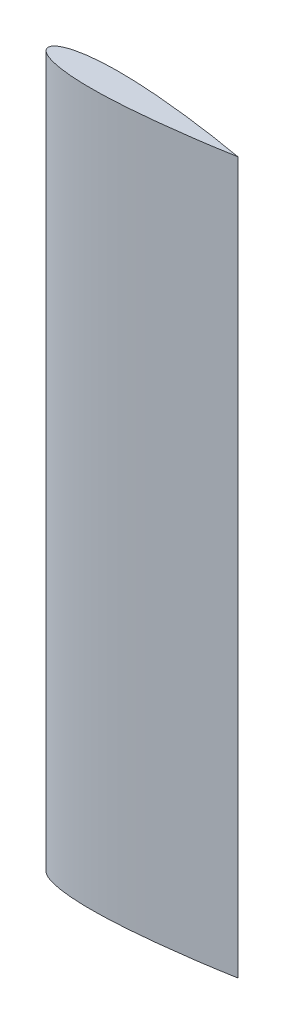
SolidWorks part; units mm, degrees
ref_plane "Front Plane" through (0, 0, 0) normal (0, 0, 1) x (1, 0, 0)
ref_plane "Top Plane" through (0, 0, 0) normal (0, 1, 0) x (1, 0, 0)
ref_plane "Right Plane" through (0, 0, 0) normal (1, 0, 0) x (0, 0, -1)
sketch "rootSketch" plane through (0, 0, 0) normal (0, 1, 0) x (1, 0, 0)
  line L0 (0, 0) -> (1500, 0) construction
  line L2 (13, -3.9) -> (13, 3.9) construction
  line L3 (0, 0) -> (52, 0) construction
  spline S0 degree 4 poles (0, 0) (0, 0.0566) (0.0054, 0.148) (0.0261, 0.2802) (0.0778, 0.4522) (0.1471, 0.6119) (0.2485, 0.786) (0.3924, 0.9775) (0.5992, 1.1954) (0.9058, 1.4518) (1.3705, 1.7579) (2.0783, 2.1191) (3.1757, 2.542) (4.8233, 2.9987) (7.2754, 3.453) (10.4387, 3.7805) (14.1293, 3.9293) (18.1436, 3.8963) (22.1517, 3.7223) (25.6562, 3.476) (28.6515, 3.2136) (31.6507, 2.914) (34.1342, 2.6396) (36.6395, 2.3366) (39.5995, 1.9537) (42.1279, 1.6007) (44.5332, 1.2475) (47.1211, 0.8374) (48.9103, 0.5455) (51.4233, 0.1075) (52.8542, -0.154) (54.9428, -0.5501) (55.9597, -0.7584) (56.7861, -0.9233) (56.9961, -0.9696) (57.2092, -1.0126) knots 0 0 0 0 0 0.003841 0.006235 0.009072 0.012193 0.015657 0.019917 0.025339 0.032593 0.042799 0.057705 0.079311 0.112503 0.158973 0.227236 0.2955 0.363764 0.432028 0.500292 0.534424 0.568556 0.63682 0.670952 0.705084 0.773347 0.807479 0.841611 0.875743 0.909875 0.954938 0.977469 0.988734 1 1 1 1 1 construction
  spline S1 degree 4 poles (0, 0) (0, 0.0566) (0.0054, 0.148) (0.0261, 0.2802) (0.0778, 0.4522) (0.1471, 0.6119) (0.2485, 0.786) (0.3924, 0.9775) (0.5992, 1.1954) (0.9058, 1.4518) (1.3705, 1.7579) (2.0783, 2.1191) (3.1757, 2.542) (4.8233, 2.9987) (7.2754, 3.453) (10.4387, 3.7805) (14.1293, 3.9293) (18.1436, 3.8963) (22.1517, 3.7223) (25.6562, 3.476) (28.6515, 3.2136) (31.6507, 2.914) (34.1342, 2.6396) (36.6395, 2.3366) (39.5995, 1.9537) (42.1279, 1.6007) (44.5332, 1.2475) (47.1211, 0.8374) (48.9103, 0.5455) (50.6553, 0.2414) (51.551, 0.0816) (52, 0) knots 0 0 0 0 0 0.003841 0.006235 0.009072 0.012193 0.015657 0.019917 0.025339 0.032593 0.042799 0.057705 0.079311 0.112503 0.158973 0.227236 0.2955 0.363764 0.432028 0.500292 0.534424 0.568556 0.63682 0.670952 0.705084 0.773347 0.807479 0.841611 0.875743 0.909875 0.909875 0.909875 0.909875 0.909875
  spline S2 degree 4 poles (0, 0) (0, -0.0566) (0.0054, -0.148) (0.0261, -0.2802) (0.0778, -0.4522) (0.1471, -0.6119) (0.2485, -0.786) (0.3924, -0.9775) (0.5992, -1.1954) (0.9058, -1.4518) (1.3705, -1.7579) (2.0783, -2.1191) (3.1757, -2.542) (4.8233, -2.9987) (7.2754, -3.453) (10.4387, -3.7805) (14.1293, -3.9293) (18.1436, -3.8963) (22.1517, -3.7223) (25.6562, -3.476) (28.6515, -3.2136) (31.6507, -2.914) (34.1342, -2.6396) (36.6395, -2.3366) (39.5995, -1.9537) (42.1279, -1.6007) (44.5332, -1.2475) (47.1211, -0.8374) (48.9103, -0.5455) (51.4233, -0.1075) (52.8542, 0.154) (54.9428, 0.5501) (55.9597, 0.7584) (56.7861, 0.9233) (56.9961, 0.9696) (57.2092, 1.0126) knots 0 0 0 0 0 0.003841 0.006235 0.009072 0.012193 0.015657 0.019917 0.025339 0.032593 0.042799 0.057705 0.079311 0.112503 0.158973 0.227236 0.2955 0.363764 0.432028 0.500292 0.534424 0.568556 0.63682 0.670952 0.705084 0.773347 0.807479 0.841611 0.875743 0.909875 0.954938 0.977469 0.988734 1 1 1 1 1 construction
  spline S3 degree 4 poles (0, 0) (0, -0.0566) (0.0054, -0.148) (0.0261, -0.2802) (0.0778, -0.4522) (0.1471, -0.6119) (0.2485, -0.786) (0.3924, -0.9775) (0.5992, -1.1954) (0.9058, -1.4518) (1.3705, -1.7579) (2.0783, -2.1191) (3.1757, -2.542) (4.8233, -2.9987) (7.2754, -3.453) (10.4387, -3.7805) (14.1293, -3.9293) (18.1436, -3.8963) (22.1517, -3.7223) (25.6562, -3.476) (28.6515, -3.2136) (31.6507, -2.914) (34.1342, -2.6396) (36.6395, -2.3366) (39.5995, -1.9537) (42.1279, -1.6007) (44.5332, -1.2475) (47.1211, -0.8374) (48.9103, -0.5455) (50.6553, -0.2414) (51.551, -0.0816) (52, 0) knots 0 0 0 0 0 0.003841 0.006235 0.009072 0.012193 0.015657 0.019917 0.025339 0.032593 0.042799 0.057705 0.079311 0.112503 0.158973 0.227236 0.2955 0.363764 0.432028 0.500292 0.534424 0.568556 0.63682 0.670952 0.705084 0.773347 0.807479 0.841611 0.875743 0.909875 0.909875 0.909875 0.909875 0.909875
  point P10 (13, 0)
  dimension "incidenceAngle" = 0
  dimension "rootChord" = 52
  dimension "rootQuarterChord" = 13
  dimension "rootMaxThickness" = 7.8
ref_plane "Plane1" through (0, 195, 0) normal (0, 1, 0) x (1, 0, 0)
sketch "tipSketch" plane through (0, 195, 0) normal (0, 1, 0) x (1, 0, 0)
  line L0 (216.8234, 0) -> (518.1352, 0) construction
  line L3 (0, 0) -> (52, 0) construction
  line L4 (13, -3.9) -> (13, 3.9) construction
  spline S0 degree 4 poles (0, 0) (0, 0.0566) (0.0054, 0.148) (0.0261, 0.2802) (0.0778, 0.4522) (0.1471, 0.6119) (0.2485, 0.786) (0.3924, 0.9775) (0.5992, 1.1954) (0.9058, 1.4518) (1.3705, 1.7579) (2.0783, 2.1191) (3.1757, 2.542) (4.8233, 2.9987) (7.2754, 3.453) (10.4387, 3.7805) (14.1293, 3.9293) (18.1436, 3.8963) (22.1517, 3.7223) (25.6562, 3.476) (28.6515, 3.2136) (31.6507, 2.914) (34.1342, 2.6396) (36.6395, 2.3366) (39.5995, 1.9537) (42.1279, 1.6007) (44.5332, 1.2475) (47.1211, 0.8374) (48.9103, 0.5455) (51.4233, 0.1075) (52.8542, -0.154) (54.9428, -0.5501) (55.9597, -0.7584) (56.7861, -0.9233) (56.9961, -0.9696) (57.2092, -1.0126) knots 0 0 0 0 0 0.003841 0.006235 0.009072 0.012193 0.015657 0.019917 0.025339 0.032593 0.042799 0.057705 0.079311 0.112503 0.158973 0.227236 0.2955 0.363764 0.432028 0.500292 0.534424 0.568556 0.63682 0.670952 0.705084 0.773347 0.807479 0.841611 0.875743 0.909875 0.954938 0.977469 0.988734 1 1 1 1 1 construction
  spline S1 degree 4 poles (0, 0) (0, 0.0566) (0.0054, 0.148) (0.0261, 0.2802) (0.0778, 0.4522) (0.1471, 0.6119) (0.2485, 0.786) (0.3924, 0.9775) (0.5992, 1.1954) (0.9058, 1.4518) (1.3705, 1.7579) (2.0783, 2.1191) (3.1757, 2.542) (4.8233, 2.9987) (7.2754, 3.453) (10.4387, 3.7805) (14.1293, 3.9293) (18.1436, 3.8963) (22.1517, 3.7223) (25.6562, 3.476) (28.6515, 3.2136) (31.6507, 2.914) (34.1342, 2.6396) (36.6395, 2.3366) (39.5995, 1.9537) (42.1279, 1.6007) (44.5332, 1.2475) (47.1211, 0.8374) (48.9103, 0.5455) (50.6553, 0.2414) (51.551, 0.0816) (52, 0) knots 0 0 0 0 0 0.003841 0.006235 0.009072 0.012193 0.015657 0.019917 0.025339 0.032593 0.042799 0.057705 0.079311 0.112503 0.158973 0.227236 0.2955 0.363764 0.432028 0.500292 0.534424 0.568556 0.63682 0.670952 0.705084 0.773347 0.807479 0.841611 0.875743 0.909875 0.909875 0.909875 0.909875 0.909875
  spline S2 degree 4 poles (0, 0) (0, -0.0566) (0.0054, -0.148) (0.0261, -0.2802) (0.0778, -0.4522) (0.1471, -0.6119) (0.2485, -0.786) (0.3924, -0.9775) (0.5992, -1.1954) (0.9058, -1.4518) (1.3705, -1.7579) (2.0783, -2.1191) (3.1757, -2.542) (4.8233, -2.9987) (7.2754, -3.453) (10.4387, -3.7805) (14.1293, -3.9293) (18.1436, -3.8963) (22.1517, -3.7223) (25.6562, -3.476) (28.6515, -3.2136) (31.6507, -2.914) (34.1342, -2.6396) (36.6395, -2.3366) (39.5995, -1.9537) (42.1279, -1.6007) (44.5332, -1.2475) (47.1211, -0.8374) (48.9103, -0.5455) (51.4233, -0.1075) (52.8542, 0.154) (54.9428, 0.5501) (55.9597, 0.7584) (56.7861, 0.9233) (56.9961, 0.9696) (57.2092, 1.0126) knots 0 0 0 0 0 0.003841 0.006235 0.009072 0.012193 0.015657 0.019917 0.025339 0.032593 0.042799 0.057705 0.079311 0.112503 0.158973 0.227236 0.2955 0.363764 0.432028 0.500292 0.534424 0.568556 0.63682 0.670952 0.705084 0.773347 0.807479 0.841611 0.875743 0.909875 0.954938 0.977469 0.988734 1 1 1 1 1 construction
  spline S3 degree 4 poles (0, 0) (0, -0.0566) (0.0054, -0.148) (0.0261, -0.2802) (0.0778, -0.4522) (0.1471, -0.6119) (0.2485, -0.786) (0.3924, -0.9775) (0.5992, -1.1954) (0.9058, -1.4518) (1.3705, -1.7579) (2.0783, -2.1191) (3.1757, -2.542) (4.8233, -2.9987) (7.2754, -3.453) (10.4387, -3.7805) (14.1293, -3.9293) (18.1436, -3.8963) (22.1517, -3.7223) (25.6562, -3.476) (28.6515, -3.2136) (31.6507, -2.914) (34.1342, -2.6396) (36.6395, -2.3366) (39.5995, -1.9537) (42.1279, -1.6007) (44.5332, -1.2475) (47.1211, -0.8374) (48.9103, -0.5455) (50.6553, -0.2414) (51.551, -0.0816) (52, 0) knots 0 0 0 0 0 0.003841 0.006235 0.009072 0.012193 0.015657 0.019917 0.025339 0.032593 0.042799 0.057705 0.079311 0.112503 0.158973 0.227236 0.2955 0.363764 0.432028 0.500292 0.534424 0.568556 0.63682 0.670952 0.705084 0.773347 0.807479 0.841611 0.875743 0.909875 0.909875 0.909875 0.909875 0.909875
  point P10 (13, 0)
  dimension "incidenceAngle" = 0
  dimension "tipChord" = 52
  dimension "tipQuarterChord" = 13
  dimension "tipMaxThickness" = 7.8
  dimension "sweepOffset" = 0
loft "Loft1" add profiles "rootSketch", "tipSketch" connector at (0, 0, 0) connector at (0, 195, 0)
ref_plane "Plane2" through (52, 0, 0) normal (1, 0, 0) x (0, 0, -1)
sketch "rudderSketch" plane through (0, 0, 0) normal (0, 0, 1) x (1, 0, 0)
  line L0 (0, 0) -> (0, 48.75) construction
  line L1 (0, 0) -> (0, 146.25) construction
  line L2 (0, 48.75) -> (26, 48.75) construction
  line L3 (0, 146.25) -> (26, 146.25) construction
  line L4 (26, 146.25) -> (26, 48.75)
  line L5 (26, 146.25) -> (78, 146.25)
  line L6 (26, 48.75) -> (78, 48.75)
  line L7 (78, 48.75) -> (78, 146.25)
  line L8 (77.61, 49.14) -> (77.61, 145.86)
  line L9 (26.39, 145.86) -> (77.61, 145.86)
  line L10 (26.39, 145.86) -> (26.39, 49.14)
  line L11 (26.39, 49.14) -> (77.61, 49.14)
  dimension "rudderStartyLoc" = 48.75
  dimension "rudderEndyLoc" = 146.25
  dimension "rudderStartxLoc" = 26
  dimension "rudderEndeLoc" = 26
  dimension "D1" = 52
  dimension "D2" = 52
  dimension "D3" = 0.39
extrude "Cut-Extrude1" [suppressed] cut sketch "rudderSketch" against normal blind 200 and the other way blind 200
equation "\"rootChord@rootSketch\"=(\"rootChord\"+\"rootChord\")/2"
equation "\"incidenceAngle@rootSketch\"=(\"incidentAngle\"+\"incidentAngle\")/2"
equation "\"rootQuarterChord@rootSketch\" = \"rootChord@rootSketch\" / 4"
equation "\"rootMaxThickness@rootSketch\" = \"rootChord\" * \"NACAairfoil\" / 100"
equation "\"halfSpan@Plane1\"= \"rootChord@rootSketch\" * ( 1 + \"taperRatio\" ) / 2 * \"aspectRatio\""
equation "\"incidenceAngle@tipSketch\" = \"incidenceAngle@rootSketch\""
equation "\"tipChord@tipSketch\"= \"rootChord@rootSketch\" * \"taperRatio\""
equation "\"tipQuarterChord@tipSketch\"=\"tipChord@tipSketch\"/4"
equation "\"tipMaxThickness@tipSketch\"=\"tipChord@tipSketch\"*\"NACAairfoil\"/100"
equation "\"rootChord@Plane2\"=\"rootChord@rootSketch\""
equation "\"rudderCenter\"= 0.5'Center of the rudder as a percentage of half span"
equation "\"rudderWidth\"= 0.5'Width of the rudder as a percentage of half span"
equation "\"rudderStartyLoc@rudderSketch\"=\"halfSpan@Plane1\" *  ( \"rudderCenter\" - \"rudderWidth\" / 2 )"
equation "\"rudderEndyLoc@rudderSketch\"=\"halfSpan@Plane1\" *  ( \"rudderCenter\" + \"rudderWidth\" / 2 )"
equation "\"rudderStartxLoc@rudderSketch\"=\"rudderStartyLoc@rudderSketch\"*tan ( \"sweepAngle\" ) + 0.5*(\"rootChord@rootSketch\" + \"rudderStartyLoc@rudderSketch\"*(((\"tipChord@tipSketch\"-\"rootChord@rootSketch\")/\"halfSpan@Plane1\")))"
equation "\"rudderEndeLoc@rudderSketch\"=\"rudderStartyLoc@rudderSketch\"*tan ( \"sweepAngle\" ) + 0.5*(\"rootChord@rootSketch\" + \"rudderStartyLoc@rudderSketch\"*(((\"tipChord@tipSketch\"-\"rootChord@rootSketch\")/\"halfSpan@Plane1\")))"
equation "\"D1@rudderSketch\"=1*\"rootChord@rootSketch\""
equation "\"D2@rudderSketch\"=1*\"rootChord@rootSketch\""
equation "\"D3@rudderSketch\"=\"halfSpan@Plane1\"/500"
equation "\"sweepOffset@tipSketch\" = \"halfSpan@Plane1\" * tan ( \"sweepAngle\" ) "
equation "\"D2@tipSketch\"=\"tipChord@tipSketch\"*tan(\"incidentAngle\")"
equation "\"rootChord\"= 0.052"
equation "\"NACAairfoil\"= 0015"
equation "\"incidentAngle\"= 0"
equation "\"aspectRatio\"= 3.75"
equation "\"taperRatio\"= 1"
equation "\"sweepAngle\"= 0"
